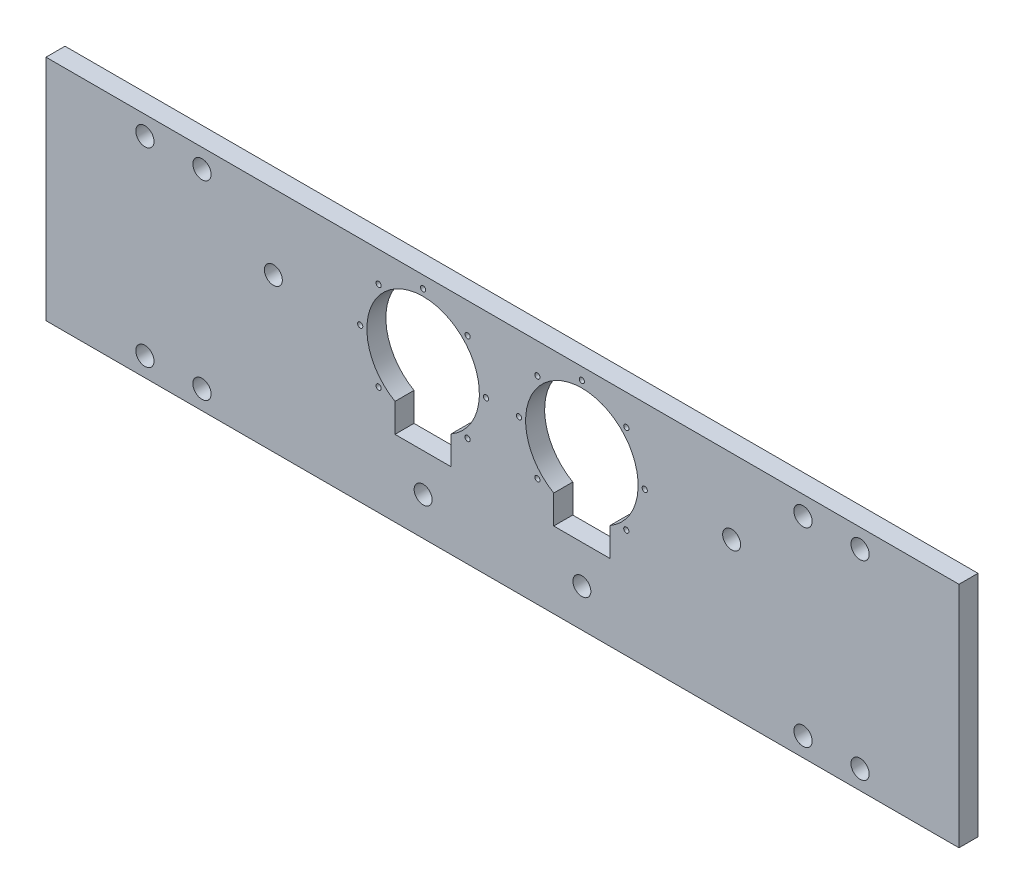
SolidWorks part; units mm, degrees
material "1060 Alloy"
ref_plane "Front Plane" through (0, 0, 0) normal (0, 0, 1) x (1, 0, 0)
ref_plane "Top Plane" through (0, 0, 0) normal (0, 1, 0) x (1, 0, 0)
ref_plane "Right Plane" through (0, 0, 0) normal (1, 0, 0) x (0, 0, -1)
sketch "Sketch1" plane through (0, 0, 0) normal (0, 0, 1) x (1, 0, 0)
  line L0 (-304.8, 0) -> (304.8, 0) construction
  line L1 (-304.8, 76.2) -> (304.8, 76.2)
  line L2 (-304.8, 76.2) -> (-304.8, -76.2)
  line L3 (-304.8, -76.2) -> (304.8, -76.2)
  line L4 (304.8, 76.2) -> (304.8, -76.2)
  line L7 (0, 76.2) -> (0, -76.2) construction
  line L8 (53, 26.2) -> (53, -11.3) construction
  line L9 (53, 26.2) -> (34.2182, -6.3309) construction
  line L10 (53, 26.2) -> (71.7818, -6.3309) construction
  line L11 (34.2182, -6.3309) -> (34.2182, -25.4)
  line L12 (71.7818, -6.3309) -> (71.7818, -25.4)
  line L13 (71.7818, -25.4) -> (34.2182, -25.4)
  line L14 (238.76, 76.2) -> (238.76, -76.2) construction
  line L15 (200.66, 76.2) -> (200.66, -76.2) construction
  line L16 (-34.2182, -6.3309) -> (-34.2182, -25.4)
  line L17 (-71.7818, -25.4) -> (-34.2182, -25.4)
  line L18 (-71.7818, -6.3309) -> (-71.7818, -25.4)
  arc A6 (71.7818, -6.3309) -> (34.2182, -6.3309) centre (53, 26.2) ccw
  circle A7 centre (53, 26.2) radius 42 construction
  circle A9 centre (82.6985, 55.8985) radius 1.746
  circle A10 centre (95, 26.2) radius 1.746
  circle A11 centre (82.6985, -3.4985) radius 1.746
  circle A13 centre (23.3015, -3.4985) radius 1.746
  circle A14 centre (11, 26.2) radius 1.746
  circle A15 centre (23.3015, 55.8985) radius 1.746
  circle A16 centre (-53, 68.2) radius 1.746
  circle A17 centre (238.76, 63.5) radius 6.096
  circle A18 centre (200.66, 63.5) radius 6.096
  circle A19 centre (238.76, -63.5) radius 6.096
  circle A20 centre (200.66, -63.5) radius 6.096
  circle A21 centre (-82.6985, -3.4985) radius 1.746
  circle A22 centre (-95, 26.2) radius 1.746
  circle A23 centre (-82.6985, 55.8985) radius 1.746
  circle A25 centre (-23.3015, 55.8985) radius 1.746
  circle A26 centre (-11, 26.2) radius 1.746
  circle A27 centre (-23.3015, -3.4985) radius 1.746
  arc A28 (-71.7818, -6.3309) -> (-34.2182, -6.3309) centre (-53, 26.2) cw
  circle A29 centre (-238.76, 63.5) radius 6.096
  circle A30 centre (-200.66, 63.5) radius 6.096
  circle A31 centre (-200.66, -63.5) radius 6.096
  circle A32 centre (-238.76, -63.5) radius 6.096
  circle A33 centre (53, 68.2) radius 1.746
  circle A34 centre (53, -50.8) radius 6
  circle A35 centre (153, 26.2) radius 6
  circle A36 centre (-153, 26.2) radius 6
  circle A37 centre (-53, -50.8) radius 6
  point P0 (0, 0)
  point P32 (53, 26.2)
  dimension "D6" = 75.127
  dimension "D7" = 84
  dimension "D15" = 12.192
  dimension "D17" = 12.192
  dimension "D8" = 3.492
  dimension "D3" = 3.492
  dimension "D20" = 12
  dimension "D21" = 12
  dimension "D1" = 609.6
  dimension "D2" = 152.4
  dimension "D4" = 53
  dimension "D5" = 50
  dimension "D10" = 30
  dimension "D11" = 30
  dimension "D12" = 50.8
  dimension "D13" = 66.04
  dimension "D14" = 38.1
  dimension "D16" = 12.7
  dimension "D18" = 12.7
  dimension "D9" = 25.4
  dimension "D19" = 53
  dimension "D22" = 100
extrude "Boss-Extrude1" add sketch "Sketch1" along normal blind 12.7
equation "\"bplate_length\"= 24in"
equation "\"bplate_height\"= 6in"
equation "\"bplate_thickness\"= 0.5in"
equation "\"motor_diameter\"= 96 / 25.4in"
equation "\"motor_clearance\"= 5 / 25.4in"
equation "\"motor_mount_hole_pattern_dia\"= 84 / 25.4in"
equation "\"motor_mount_hole_dia\"= 4 / 25.4in"
equation "\"motor_cx\"= \"motor_clearance\" + \"motor_diameter\" / 2in"
equation "\"motor_cy_top\"= \"motor_mount_hole_pattern_dia\" / 2 + \"motor_mount_hole_dia\" * 2in"
equation "\"D1@Sketch1\"=\"bplate_length\""
equation "\"D2@Sketch1\"=\"bplate_height\""
equation "\"motor_driver_cover_dia\"= 75 / 25.4in"
equation "\"D4@Sketch1\"=\"motor_cx\""
equation "\"motor_driver_cutout_clearance\"= 60deg"
equation "\"wire_cutout_clearance\"= 2in"
equation "\"connector_plate_thickness\"= 1in"
equation "\"connector_plate_hole_diameter\"= 0.5in"
equation "\"connector_plate_hole_depth\"= 1in"
equation "\"coonector_first_hole_offset\"= 1.6in"
equation "\"D14@Sketch1\"=1.5"
equation "\"D13@Sketch1\"=\"coonector_first_hole_offset\"+1in"
equation "\"D12@Sketch1\"=\"wire_cutout_clearance\""
equation "\"D16@Sketch1\"=\"connector_plate_thickness\"/2"
equation "\"D18@Sketch1\"=\"connector_plate_thickness\"/2"
equation "\"D15@Sketch1\"=\"connector_plate_hole_diameter\"- 0.02"
equation "\"D17@Sketch1\"=\"connector_plate_hole_diameter\"-0.02"
equation "\"D6@Sketch1\"=\"motor_driver_cover_dia\"+0.005"
equation "\"D7@Sketch1\"=\"motor_mount_hole_pattern_dia\""
equation "\"D3@Sketch1\"=\"motor_mount_hole_dia\" - 0.02"
equation "\"D9@Sketch1\"=\"wire_cutout_clearance\"/2"
equation "\"D19@Sketch1\"=\"motor_cx\""
